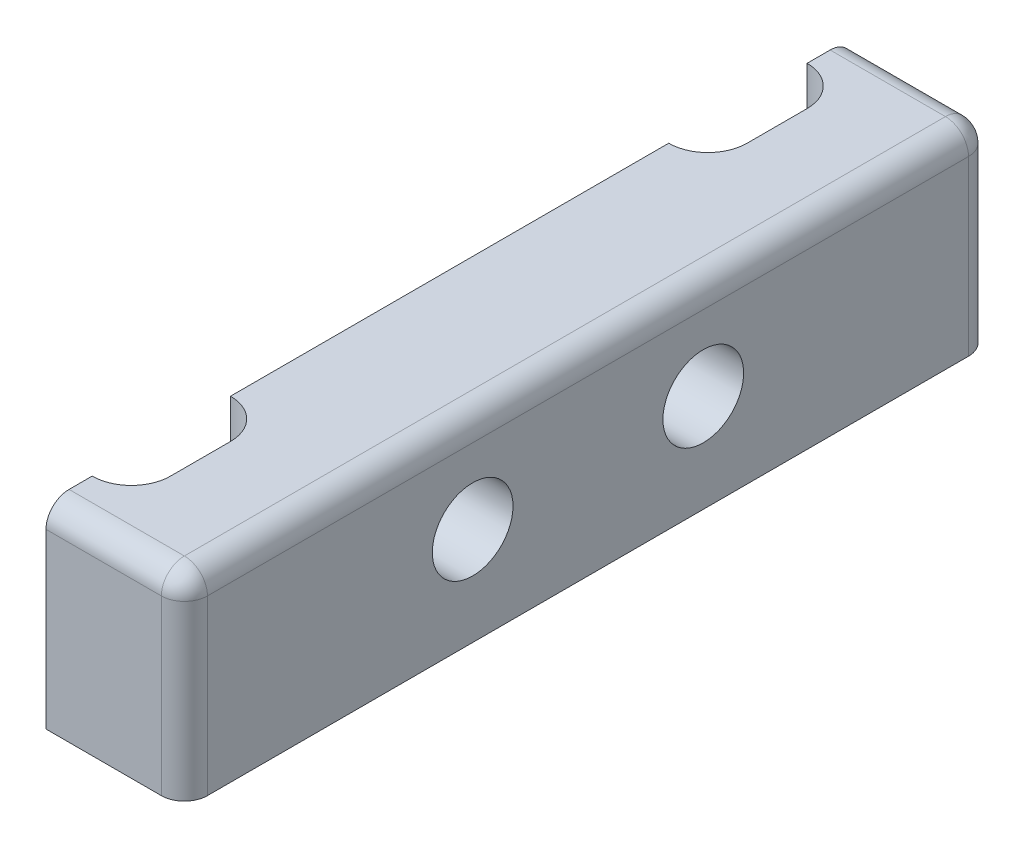
SolidWorks part; units mm, degrees
ref_plane "Front Plane" through (0, 0, 0) normal (0, 0, 1) x (1, 0, 0)
ref_plane "Top Plane" through (0, 0, 0) normal (0, 1, 0) x (1, 0, 0)
ref_plane "Right Plane" through (0, 0, 0) normal (1, 0, 0) x (0, 0, -1)
sketch "Sketch1" plane through (0, 0, 0) normal (0, 1, 0) x (1, 0, 0)
  line L0 (-6, 17.5) -> (-6, 15.5)
  line L1 (-6, 17.5) -> (0, 17.5)
  line L3 (-6, -17.5) -> (0, -17.5)
  line L4 (0, 17.5) -> (0, -17.5)
  line L5 (-6, 9.5) -> (-6, -9.5)
  line L6 (-6, -17.5) -> (-6, -15.5)
  line L7 (-4.3, -13.8) -> (-4.3, -11.2)
  line L8 (-4.3, 11.2) -> (-4.3, 13.8)
  arc A0 (-4.3, 13.8) -> (-6, 15.5) centre (-6, 13.8) ccw
  arc A1 (-4.3, 11.2) -> (-6, 9.5) centre (-6, 11.2) cw
  arc A2 (-4.3, -11.2) -> (-6, -9.5) centre (-6, -11.2) ccw
  arc A3 (-4.3, -13.8) -> (-6, -15.5) centre (-6, -13.8) cw
  point P4 (0, 0)
  point P20 (-4.3, 12.5)
  point P21 (-4.3, -12.5)
  dimension "D4" = 1.7
  dimension "D1" = 35
  dimension "D2" = 6
  dimension "D3" = 2
  dimension "D5" = 6
  dimension "D6" = 2.6
  dimension "D7" = 25
  dimension "D8" = 6
extrude "Base" add sketch "Sketch1" along normal blind 8.5
sketch "Sketch2" plane through (-6, 0, 0) normal (-1, 0, 0) x (0, 0, 1)
  line L0 (-9.5, 4.25) -> (9.5, 4.25) construction
  line L1 (-9.5, 8.5) -> (-9.5, 0) construction
  line L2 (9.5, 8.5) -> (9.5, 0) construction
  line L3 (0, 8.5) -> (0, 0) construction
  line L4 (-9.5, 8.5) -> (9.5, 8.5) construction
  circle A0 centre (-5, 4.25) radius 1.75
  circle A1 centre (5, 4.25) radius 1.75
  dimension "D1" = 4.5
  dimension "D2" = 3.5
extrude "Screw Holes" cut sketch "Sketch2" against normal through all
fillet "1mm Edge Fillets" radius 1 5 edges at (0, 4.25, -17.5) (-3, 8.5, -17.5) (0, 8.5, 0) (0, 4.25, 17.5) (-3, 8.5, 17.5)
